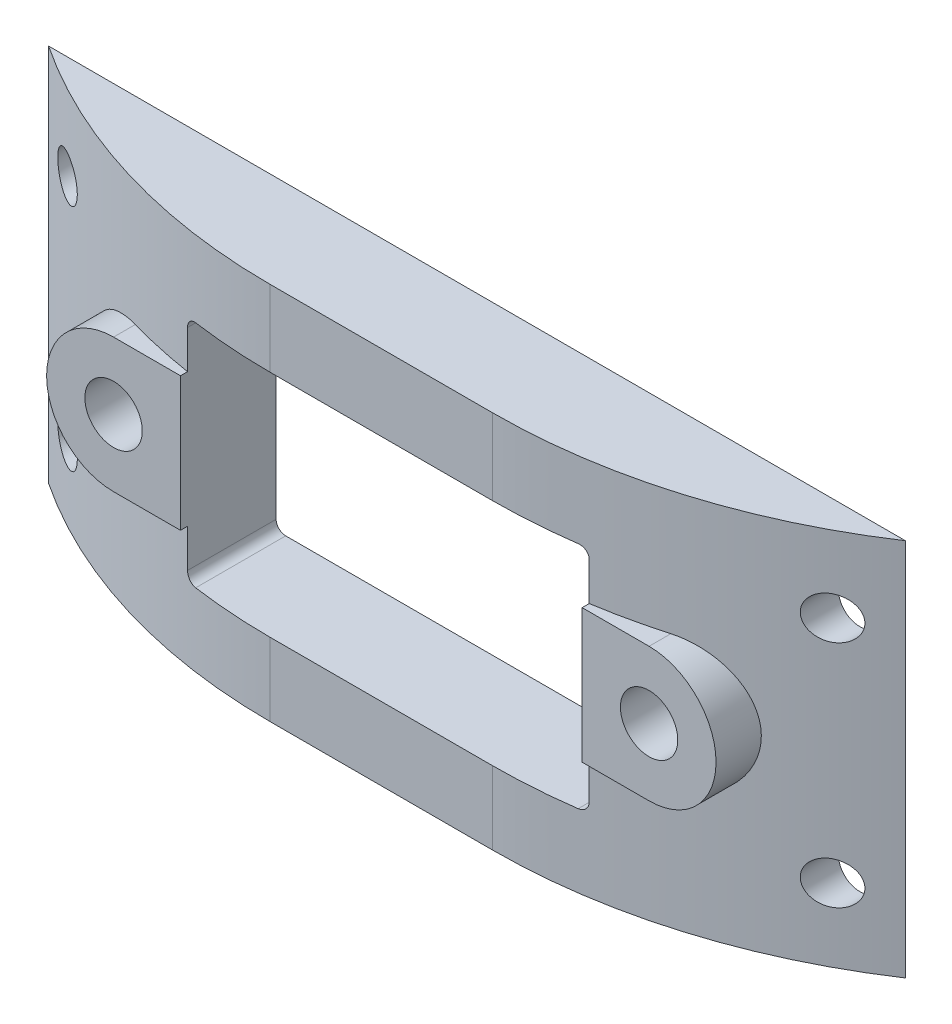
SolidWorks part; units mm, degrees
ref_plane "Front Plane" through (0, 0, 0) normal (0, 0, 1) x (1, 0, 0)
ref_plane "Top Plane" through (0, 0, 0) normal (0, 1, 0) x (1, 0, 0)
ref_plane "Right Plane" through (0, 0, 0) normal (1, 0, 0) x (0, 0, -1)
sketch "Sketch1" plane through (0, 0, 0) normal (0, 0, 1) x (1, 0, 0)
  line L1 (-22.4, 9.18) -> (22.4, 9.18)
  line L2 (-22.4, 9.18) -> (-22.4, 28.98)
  line L3 (-22.4, 28.98) -> (22.4, 28.98)
  line L4 (22.4, 9.18) -> (22.4, 28.98)
  dimension "D1" = 44.8
  dimension "D2" = 19.8
  dimension "D3" = 22.4
extrude "Boss-Extrude1" add sketch "Sketch1" along normal blind 5
sketch "Sketch2" plane through (0, 0, 5) normal (0, 0, 1) x (1, 0, 0)
  circle A0 centre (-20, 25) radius 1.1
  circle A1 centre (-20, 13) radius 1.1
  circle A2 centre (20, 25) radius 1.1
  circle A3 centre (20, 13) radius 1.1
  dimension "D6" = 2.2
  dimension "D7" = 2.2
  dimension "D8" = 2.2
  dimension "D9" = 2.2
  dimension "D1" = 13
  dimension "D2" = 12
  dimension "D3" = 12
  dimension "D4" = 40
  dimension "D5" = 13
  dimension "D10" = 20
  dimension "D11" = 40
  dimension "D12" = 20
extrude "Cut-Extrude1" cut sketch "Sketch2" against normal blind 13
sketch "Sketch3" plane through (0, 0, 5) normal (0, 0, 1) x (1, 0, 0)
  circle A0 centre (-14, 19) radius 1.5
  circle A1 centre (14, 19) radius 1.5
  dimension "D4" = 3
  dimension "D5" = 3
  dimension "D1" = 28
  dimension "D2" = 14
  dimension "D3" = 19
extrude "Cut-Extrude2" cut sketch "Sketch3" against normal blind 10
sketch "Sketch4" plane through (0, 0, 5) normal (0, 0, 1) x (1, 0, 0)
  line L1 (-10.5, 25) -> (10.5, 25)
  line L2 (-10.5, 25) -> (-10.5, 13)
  line L3 (-10.5, 13) -> (10.5, 13)
  line L4 (10.5, 25) -> (10.5, 13)
  dimension "D1" = 21
  dimension "D2" = 12
  dimension "D3" = 10.5
  dimension "D4" = 13
extrude "Cut-Extrude3" cut sketch "Sketch4" against normal blind 10
fillet "Fillet1" radius 30 2 edges at (22.4, 19.08, 5) (-22.4, 19.08, 5)
sketch "Sketch5" plane through (0, 0, 0) normal (0, 0, -1) x (-1, 0, 0)
  line L0 (-14, 22.5) -> (-10.5, 22.5)
  line L1 (-10.5, 25) -> (-10.5, 13) construction
  line L2 (-10.5, 22.5) -> (-10.5, 15.5)
  line L3 (-10.5, 15.5) -> (-14, 15.5)
  line L4 (14, 22.5) -> (10.5, 22.5)
  line L5 (10.5, 13) -> (10.5, 25) construction
  line L6 (10.5, 22.5) -> (10.5, 15.5)
  line L7 (10.5, 15.5) -> (14, 15.5)
  circle A0 centre (-14, 19) radius 3.5
  circle A1 centre (14, 19) radius 3.5
  line M1 (10.5, 25) -> (10.5, 13)
  line M3 (-10.5, 13) -> (-10.5, 25)
  circle M5 centre (14, 19) radius 1.5
  circle M6 centre (-14, 19) radius 1.5
extrude "Boss-Extrude2" add sketch "Sketch5" against normal blind 5 contours A0 M6 | A0 L2 L0 | A0 L3 M3 | A1 M5 | A1 L6 L7 | A1 L4 M1 region at (11.2818, 21.7182, 0) region at (11.5951, 21.4049, 0) region at (11.2818, 16.2818, 0) region at (-11.2818, 21.7182, 0) region at (-16.4049, 21.4049, 0) region at (-11.2818, 16.2818, 0)
fillet "Fillet2" radius 0.5 4 edges at (10.5, 25, 2.3161) (10.5, 13, 2.3161) (-10.5, 13, 2.3161) (-10.5, 25, 2.3161)
